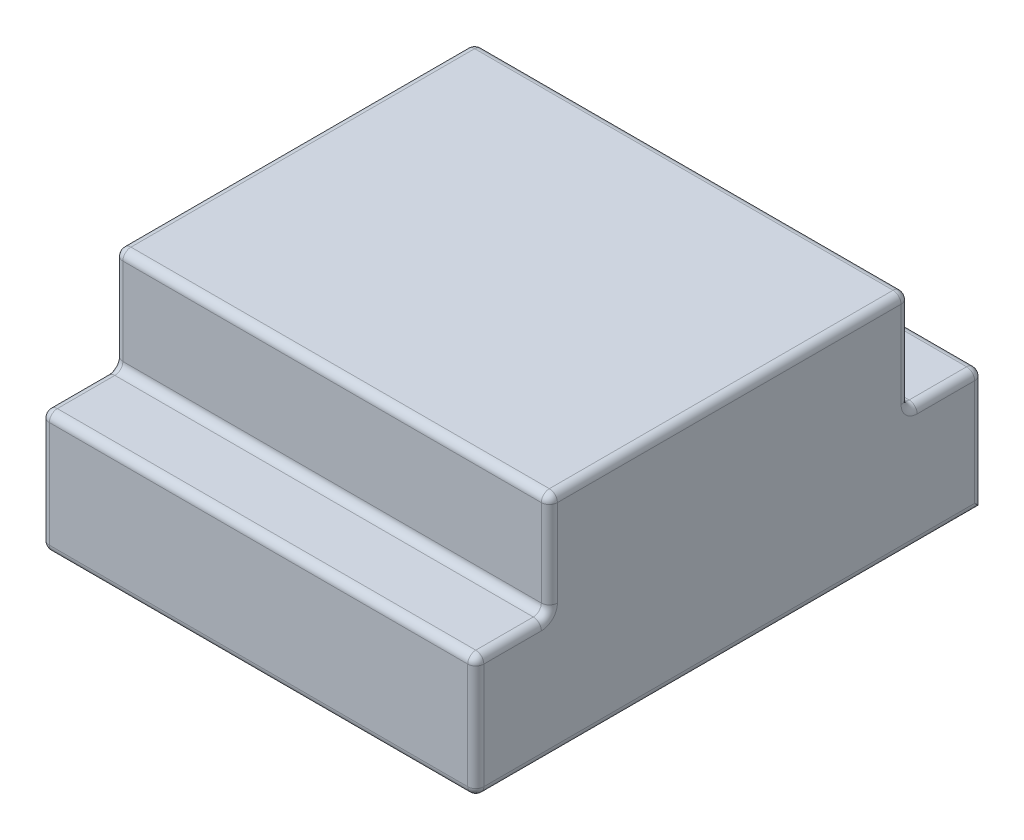
SolidWorks part; units mm, degrees
ref_plane "Front Plane" through (0, 0, 0) normal (0, 0, 1) x (1, 0, 0)
ref_plane "Top Plane" through (0, 0, 0) normal (0, 1, 0) x (1, 0, 0)
ref_plane "Right Plane" through (0, 0, 0) normal (1, 0, 0) x (0, 0, -1)
sketch "Sketch1" plane through (0, 0, 0) normal (0, 1, 0) x (1, 0, 0)
  line L0 (0, 0) -> (-68.58, 0) construction
  line L1 (-68.58, 0) -> (-68.58, 80.01) construction
  line L2 (-68.58, 80.01) -> (68.58, 80.01)
  line L3 (68.58, 80.01) -> (68.58, -80.01)
  line L4 (68.58, -80.01) -> (-68.58, -80.01)
  line L5 (-68.58, -80.01) -> (-68.58, 80.01)
  dimension "D1" = 68.58
  dimension "D2" = 80.01
  dimension "D3" = 160.02
  dimension "D4" = 137.16
extrude "Boss-Extrude1" add sketch "Sketch1" against normal blind 71.12
sketch "Sketch2" plane through (68.58, 0, 0) normal (1, 0, 0) x (0, 0, -1)
  line L0 (0, 0) -> (0, -32.5292) construction
  line L1 (-80.01, 0) -> (80.01, 0) construction
  line L2 (0, -32.5292) -> (-80.01, -32.5292) construction
  line L3 (-80.01, -71.12) -> (-80.01, 0) construction
  line L4 (-80.01, -32.5292) -> (-56.7827, -32.5292)
  line L5 (-56.7827, -32.5292) -> (-56.7827, 0)
  line L6 (-56.7827, 0) -> (-80.01, 0)
  line L7 (-80.01, 0) -> (-80.01, -32.5292)
  line L8 (56.7827, 0) -> (80.01, 0)
  line L9 (56.7827, -32.5292) -> (56.7827, 0)
  line L10 (80.01, -32.5292) -> (56.7827, -32.5292)
  line L11 (80.01, 0) -> (80.01, -32.5292)
  dimension "D1" = 32.5292
  dimension "D2" = 23.2273
extrude "Cut-Extrude1" cut sketch "Sketch2" against normal through all both and the other way through all
fillet "Fillet1" radius 2.54 21 edges at (-68.58, -16.2646, -56.7827) (-68.58, -16.2646, 56.7827) (0, -71.12, 80.01) (-68.58, -51.8246, 80.01) (68.58, -16.2646, -56.7827) (68.58, -51.8246, -80.01) (68.58, -71.12, 0) (68.58, -51.8246, 80.01) (68.58, -16.2646, 56.7827) (0, -32.5292, -56.7827) (-68.58, -32.5292, -68.3963) (0, -32.5292, -80.01) (68.58, -32.5292, -68.3963) (0, 0, -56.7827) (68.58, 0, 0) (0, 0, 56.7827) (-68.58, 0, 0) (0, -32.5292, 80.01) (-68.58, -32.5292, 68.3963) (0, -32.5292, 56.7827) (68.58, -32.5292, 68.3963)
fillet "Fillet2" radius 2.54 4 edges at (-67.8361, -70.3761, 79.2661) (-67.8361, -33.2732, -79.2661) (-68.58, -71.12, -1.27) (-68.58, -53.0946, -80.01)
sketch "Sketch3" plane through (0, -71.12, 0) normal (0, -1, 0) x (1, 0, 0)
  line L0 (-66.04, 78.74) -> (-66.04, -57.4675) construction
  line L1 (-66.04, 80.01) -> (-66.04, 77.47) construction
  line L2 (-66.04, 77.47) -> (-66.04, -80.01) construction
  line L3 (-66.04, -57.4675) -> (-22.2504, -57.4675) construction
  line L4 (0, 0) -> (-59.9206, 0) construction
  line L5 (0, 0) -> (0, -47.9562) construction
  circle A0 centre (-22.2504, -57.4675) radius 3.302
  circle A1 centre (-22.2504, 57.4675) radius 3.302
  circle A2 centre (22.2504, 57.4675) radius 3.302
  circle A3 centre (22.2504, -57.4675) radius 3.302
  dimension "D3" = 6.604
  dimension "D1" = 136.2075
  dimension "D2" = 43.7896
extrude "Cut-Extrude2" cut sketch "Sketch3" against normal blind 7.62
